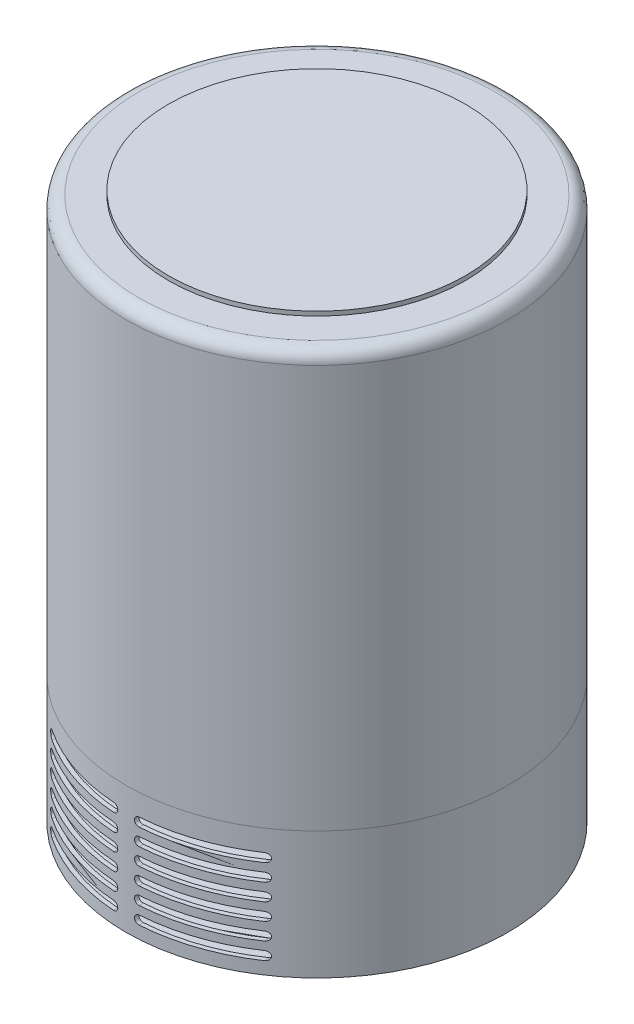
SolidWorks part; units mm, degrees
ref_plane "Front Plane" through (0, 0, 0) normal (0, 0, 1) x (1, 0, 0)
ref_plane "Top Plane" through (0, 0, 0) normal (0, 1, 0) x (1, 0, 0)
ref_plane "Right Plane" through (0, 0, 0) normal (1, 0, 0) x (0, 0, -1)
sketch "Sketch1" plane through (0, 0, 0) normal (0, 1, 0) x (1, 0, 0)
  circle A0 centre (0, 0) radius 45
  dimension "D1" = 90
extrude "Boss-Extrude1" add sketch "Sketch1" along normal blind 98
fillet "Fillet1" radius 3 1 edges at (0, 98, 45)
sketch "Sketch2" plane through (0, 0, 0) normal (0, -1, 0) x (1, 0, 0)
  circle A0 centre (0, 0) radius 44
  dimension "D1" = 88
extrude "Cut-Extrude1" cut sketch "Sketch2" against normal blind 97
sketch "Sketch5" plane through (0, 0, 0) normal (0, 1, 0) x (1, 0, 0)
  circle A0 centre (0, 0) radius 45
  dimension "D1" = 90
extrude "Boss-Extrude6" add sketch "Sketch5" against normal blind 30 separate body
sketch "Sketch6" plane through (0, 0, 0) normal (0, 1, 0) x (1, 0, 0)
  circle A0 centre (0, 0) radius 44
  dimension "D1" = 88
extrude "Cut-Extrude2" cut sketch "Sketch6" against normal blind 29
sketch "Sketch7" plane through (0, 98, 0) normal (0, 1, 0) x (1, 0, 0)
  circle A0 centre (0, 0) radius 35
  dimension "D1" = 70
extrude "Boss-Extrude7" add sketch "Sketch7" along normal blind 1
sketch "Sketch8" plane through (0, 0, 0) normal (1, 0, 0) x (0, 0, -1)
  line L0 (45, -15) -> (-47.6224, -15) construction
  line L1 (45, -30) -> (45, 0) construction
  line L3 (3.5, -16.75) -> (-3.5, -16.75)
  line L4 (3.5, -16.75) -> (3.5, -13.25)
  line L5 (3.5, -13.25) -> (-3.5, -13.25)
  line L6 (-3.5, -16.75) -> (-3.5, -13.25)
  line L7 (3.5, -16.75) -> (-3.5, -13.25) construction
  line L8 (3.5, -13.25) -> (-3.5, -16.75) construction
  point P4 (0, -15)
  dimension "D1" = 7
  dimension "D2" = 3.5
extrude "Cut-Extrude3" cut sketch "Sketch8" against normal through all from offset 39 offset against normal yes
sketch "Sketch10" plane through (0, 0, 0) normal (0, 0, 1) x (1, 0, 0)
  line L0 (25, -6.0288) -> (3, -6.0288) construction
  line L5 (0, 12.9357) -> (0, -57.2827) construction
  line L30 (25, -5) -> (3, -5)
  line L31 (25, -7.0576) -> (3, -7.0576)
  line L32 (-25, -6.0288) -> (-3, -6.0288) construction
  line L33 (-25, -5) -> (-3, -5)
  line L34 (-25, -7.0576) -> (-3, -7.0576)
  line L35 (-25, -10.0288) -> (-3, -10.0288) construction
  line L36 (-25, -9) -> (-3, -9)
  line L37 (-25, -11.0576) -> (-3, -11.0576)
  line L38 (25, -10.0288) -> (3, -10.0288) construction
  line L39 (25, -9) -> (3, -9)
  line L40 (25, -11.0576) -> (3, -11.0576)
  line L41 (-25, -14.0288) -> (-3, -14.0288) construction
  line L42 (-25, -13) -> (-3, -13)
  line L43 (-25, -15.0576) -> (-3, -15.0576)
  line L44 (25, -14.0288) -> (3, -14.0288) construction
  line L45 (25, -13) -> (3, -13)
  line L46 (25, -15.0576) -> (3, -15.0576)
  line L47 (-25, -18.0288) -> (-3, -18.0288) construction
  line L48 (-25, -17) -> (-3, -17)
  line L49 (-25, -19.0576) -> (-3, -19.0576)
  line L50 (25, -18.0288) -> (3, -18.0288) construction
  line L51 (25, -17) -> (3, -17)
  line L52 (25, -19.0576) -> (3, -19.0576)
  line L53 (-25, -22.0288) -> (-3, -22.0288) construction
  line L54 (-25, -21) -> (-3, -21)
  line L55 (-25, -23.0576) -> (-3, -23.0576)
  line L56 (25, -22.0288) -> (3, -22.0288) construction
  line L57 (25, -21) -> (3, -21)
  line L58 (25, -23.0576) -> (3, -23.0576)
  line L59 (-25, -26.0288) -> (-3, -26.0288) construction
  line L60 (-25, -25) -> (-3, -25)
  line L61 (-25, -27.0576) -> (-3, -27.0576)
  line L62 (25, -26.0288) -> (3, -26.0288) construction
  line L63 (25, -25) -> (3, -25)
  line L64 (25, -27.0576) -> (3, -27.0576)
  line L65 (45, 0) -> (-45, 0) construction
  arc A0 (-25, -5) -> (-25, -7.0576) centre (-25, -6.0288) ccw
  arc A1 (-3, -7.0576) -> (-3, -5) centre (-3, -6.0288) ccw
  arc A2 (25, -5) -> (25, -7.0576) centre (25, -6.0288) cw
  arc A3 (3, -7.0576) -> (3, -5) centre (3, -6.0288) cw
  arc A4 (-25, -9) -> (-25, -11.0576) centre (-25, -10.0288) ccw
  arc A5 (-3, -11.0576) -> (-3, -9) centre (-3, -10.0288) ccw
  arc A6 (25, -9) -> (25, -11.0576) centre (25, -10.0288) cw
  arc A7 (3, -11.0576) -> (3, -9) centre (3, -10.0288) cw
  arc A8 (-25, -13) -> (-25, -15.0576) centre (-25, -14.0288) ccw
  arc A9 (-3, -15.0576) -> (-3, -13) centre (-3, -14.0288) ccw
  arc A10 (25, -13) -> (25, -15.0576) centre (25, -14.0288) cw
  arc A11 (3, -15.0576) -> (3, -13) centre (3, -14.0288) cw
  arc A12 (-25, -17) -> (-25, -19.0576) centre (-25, -18.0288) ccw
  arc A13 (-3, -19.0576) -> (-3, -17) centre (-3, -18.0288) ccw
  arc A14 (25, -17) -> (25, -19.0576) centre (25, -18.0288) cw
  arc A15 (3, -19.0576) -> (3, -17) centre (3, -18.0288) cw
  arc A16 (-25, -21) -> (-25, -23.0576) centre (-25, -22.0288) ccw
  arc A17 (-3, -23.0576) -> (-3, -21) centre (-3, -22.0288) ccw
  arc A18 (25, -21) -> (25, -23.0576) centre (25, -22.0288) cw
  arc A19 (3, -23.0576) -> (3, -21) centre (3, -22.0288) cw
  arc A20 (-25, -25) -> (-25, -27.0576) centre (-25, -26.0288) ccw
  arc A21 (-3, -27.0576) -> (-3, -25) centre (-3, -26.0288) ccw
  arc A22 (25, -25) -> (25, -27.0576) centre (25, -26.0288) cw
  arc A23 (3, -27.0576) -> (3, -25) centre (3, -26.0288) cw
  point P3 (14, -6.0288)
  point P7 (-14, -6.0288)
  point P19 (14, -10.0288)
  point P22 (-14, -10.0288)
  point P33 (14, -14.0288)
  point P36 (-14, -14.0288)
  point P47 (14, -18.0288)
  point P50 (-14, -18.0288)
  point P61 (14, -22.0288)
  point P64 (-14, -22.0288)
  point P75 (14, -26.0288)
  point P78 (-14, -26.0288)
  dimension "D1" = 22
  dimension "D2" = 6
  dimension "D3" = 5
extrude "Cut-Extrude5" cut sketch "Sketch10" against normal blind 10 from offset 36 offset against normal yes
sketch "Sketch12" plane through (0, 0, 0) normal (0, 0, 1) x (1, 0, 0)
  line L0 (25, -6.0288) -> (3, -6.0288) construction
  line L5 (0, 12.9357) -> (0, -57.2827) construction
  line L30 (25, -5) -> (3, -5)
  line L31 (25, -7.0576) -> (3, -7.0576)
  line L32 (-25, -6.0288) -> (-3, -6.0288) construction
  line L33 (-25, -5) -> (-3, -5)
  line L34 (-25, -7.0576) -> (-3, -7.0576)
  line L35 (-25, -10.0288) -> (-3, -10.0288) construction
  line L36 (-25, -9) -> (-3, -9)
  line L37 (-25, -11.0576) -> (-3, -11.0576)
  line L38 (25, -10.0288) -> (3, -10.0288) construction
  line L39 (25, -9) -> (3, -9)
  line L40 (25, -11.0576) -> (3, -11.0576)
  line L41 (-25, -14.0288) -> (-3, -14.0288) construction
  line L42 (-25, -13) -> (-3, -13)
  line L43 (-25, -15.0576) -> (-3, -15.0576)
  line L44 (25, -14.0288) -> (3, -14.0288) construction
  line L45 (25, -13) -> (3, -13)
  line L46 (25, -15.0576) -> (3, -15.0576)
  line L47 (-25, -18.0288) -> (-3, -18.0288) construction
  line L48 (-25, -17) -> (-3, -17)
  line L49 (-25, -19.0576) -> (-3, -19.0576)
  line L50 (25, -18.0288) -> (3, -18.0288) construction
  line L51 (25, -17) -> (3, -17)
  line L52 (25, -19.0576) -> (3, -19.0576)
  line L53 (-25, -22.0288) -> (-3, -22.0288) construction
  line L54 (-25, -21) -> (-3, -21)
  line L55 (-25, -23.0576) -> (-3, -23.0576)
  line L56 (25, -22.0288) -> (3, -22.0288) construction
  line L57 (25, -21) -> (3, -21)
  line L58 (25, -23.0576) -> (3, -23.0576)
  line L59 (-25, -26.0288) -> (-3, -26.0288) construction
  line L60 (-25, -25) -> (-3, -25)
  line L61 (-25, -27.0576) -> (-3, -27.0576)
  line L62 (25, -26.0288) -> (3, -26.0288) construction
  line L63 (25, -25) -> (3, -25)
  line L64 (25, -27.0576) -> (3, -27.0576)
  line L65 (45, 0) -> (-45, 0) construction
  arc A0 (-25, -5) -> (-25, -7.0576) centre (-25, -6.0288) ccw
  arc A1 (-3, -7.0576) -> (-3, -5) centre (-3, -6.0288) ccw
  arc A2 (25, -5) -> (25, -7.0576) centre (25, -6.0288) cw
  arc A3 (3, -7.0576) -> (3, -5) centre (3, -6.0288) cw
  arc A4 (-25, -9) -> (-25, -11.0576) centre (-25, -10.0288) ccw
  arc A5 (-3, -11.0576) -> (-3, -9) centre (-3, -10.0288) ccw
  arc A6 (25, -9) -> (25, -11.0576) centre (25, -10.0288) cw
  arc A7 (3, -11.0576) -> (3, -9) centre (3, -10.0288) cw
  arc A8 (-25, -13) -> (-25, -15.0576) centre (-25, -14.0288) ccw
  arc A9 (-3, -15.0576) -> (-3, -13) centre (-3, -14.0288) ccw
  arc A10 (25, -13) -> (25, -15.0576) centre (25, -14.0288) cw
  arc A11 (3, -15.0576) -> (3, -13) centre (3, -14.0288) cw
  arc A12 (-25, -17) -> (-25, -19.0576) centre (-25, -18.0288) ccw
  arc A13 (-3, -19.0576) -> (-3, -17) centre (-3, -18.0288) ccw
  arc A14 (25, -17) -> (25, -19.0576) centre (25, -18.0288) cw
  arc A15 (3, -19.0576) -> (3, -17) centre (3, -18.0288) cw
  arc A16 (-25, -21) -> (-25, -23.0576) centre (-25, -22.0288) ccw
  arc A17 (-3, -23.0576) -> (-3, -21) centre (-3, -22.0288) ccw
  arc A18 (25, -21) -> (25, -23.0576) centre (25, -22.0288) cw
  arc A19 (3, -23.0576) -> (3, -21) centre (3, -22.0288) cw
  arc A20 (-25, -25) -> (-25, -27.0576) centre (-25, -26.0288) ccw
  arc A21 (-3, -27.0576) -> (-3, -25) centre (-3, -26.0288) ccw
  arc A22 (25, -25) -> (25, -27.0576) centre (25, -26.0288) cw
  arc A23 (3, -27.0576) -> (3, -25) centre (3, -26.0288) cw
  point P3 (14, -6.0288)
  point P7 (-14, -6.0288)
  point P19 (14, -10.0288)
  point P22 (-14, -10.0288)
  point P33 (14, -14.0288)
  point P36 (-14, -14.0288)
  point P47 (14, -18.0288)
  point P50 (-14, -18.0288)
  point P61 (14, -22.0288)
  point P64 (-14, -22.0288)
  point P75 (14, -26.0288)
  point P78 (-14, -26.0288)
  dimension "D1" = 22
  dimension "D2" = 6
  dimension "D3" = 5
extrude "Cut-Extrude6" cut sketch "Sketch12" against normal blind 10 from offset 46
